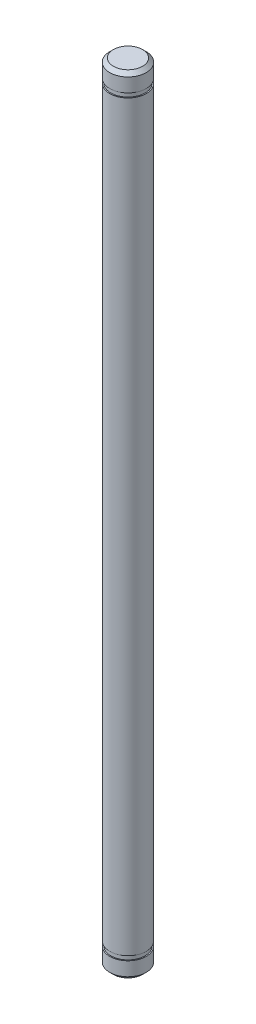
SolidWorks part; units mm, degrees
ref_plane "前视基准面" through (0, 0, 0) normal (0, 0, 1) x (1, 0, 0)
ref_plane "上视基准面" through (0, 0, 0) normal (0, 1, 0) x (1, 0, 0)
ref_plane "右视基准面" through (0, 0, 0) normal (1, 0, 0) x (0, 0, -1)
other "Configuration Table"
sketch "草图1" plane through (0, 0, 0) normal (0, 1, 0) x (1, 0, 0)
  circle A0 centre (0, 0) radius 2.5
  dimension "D1" = 5
extrude "凸台-拉伸1" add sketch "草图1" along normal blind 108
chamfer "倒角1" distance 0.5 angle 45 2 edges at (0, 0, 2.5) (0, 108, 2.5)
ref_plane "基准面1" through (0, 54, 0) normal (0, 1, 0) x (1, 0, 0)
sketch "草图2" plane through (0, 108, 0) normal (0, 1, 0) x (1, 0, 0)
  circle A0 centre (0, 0) radius 2.5 construction
  circle A1 centre (0, 0) radius 2.5
  circle A2 centre (0, 0) radius 2.35
  dimension "D1" = 4.7
extrude "切除-拉伸1" cut sketch "草图2" along normal blind 0.6 from offset 3 offset against normal yes
mirror "镜向1" about plane through (0, 54, 0) normal (0, 1, 0) of "切除-拉伸1"
